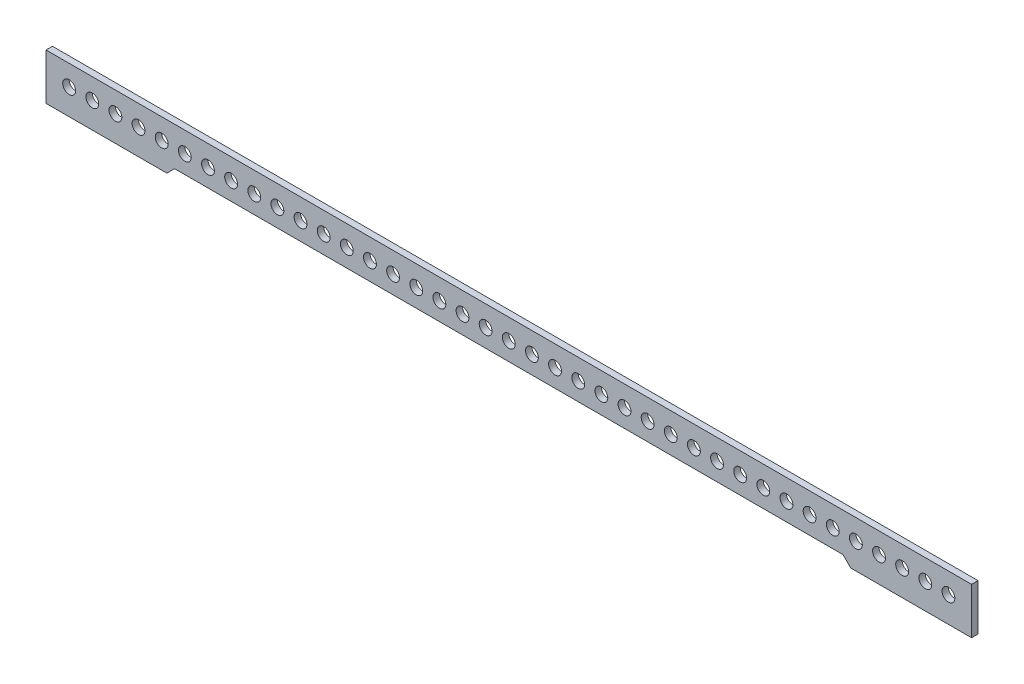
SolidWorks part; units mm, degrees
ref_plane "Front Plane" through (0, 0, 0) normal (0, 0, 1) x (1, 0, 0)
ref_plane "Top Plane" through (0, 0, 0) normal (0, 1, 0) x (1, 0, 0)
ref_plane "Right Plane" through (0, 0, 0) normal (1, 0, 0) x (0, 0, -1)
sketch "Sketch1" plane through (0, 0, 0) normal (0, 0, 1) x (1, 0, 0)
  line L0 (-228.6, 0) -> (228.6, 0)
  line L2 (228.6, -22.86) -> (168.91, -22.86)
  line L3 (168.91, -22.86) -> (165.1, -19.05)
  line L4 (165.1, -19.05) -> (-165.1, -19.05)
  line L5 (-165.1, -19.05) -> (-168.91, -22.86)
  line L6 (-168.91, -22.86) -> (-228.6, -22.86)
  line L8 (-228.6, -22.86) -> (-228.6, 0)
  line L9 (228.6, 0) -> (228.6, -22.86)
  point P0 (-165.1, -24.7914)
  dimension "D1" = 457.2
  dimension "D2" = 22.86
  dimension "D3" = 330.2
  dimension "D4" = 3.81
extrude "Boss-Extrude1" add sketch "Sketch1" along normal blind 3.175
sketch "Sketch3" plane through (0, 0, 3.175) normal (0, 0, 1) x (1, 0, 0)
  line L0 (228.6, 0) -> (-228.6, 0) construction
  line L1 (-217.17, -10.16) -> (-228.6, -10.16) construction
  line L2 (-217.17, -10.16) -> (-205.74, -10.16) construction
  line L3 (217.17, -10.16) -> (228.6, -10.16) construction
  line L4 (-228.6, 0) -> (-228.6, -22.86) construction
  line L5 (228.6, -22.86) -> (228.6, 0) construction
  circle A0 centre (-217.17, -10.16) radius 3.175
  circle A1 centre (-205.74, -10.16) radius 3.175
  circle A2 centre (-194.31, -10.16) radius 3.175
  circle A3 centre (-182.88, -10.16) radius 3.175
  circle A4 centre (-171.45, -10.16) radius 3.175
  circle A5 centre (-160.02, -10.16) radius 3.175
  circle A6 centre (-148.59, -10.16) radius 3.175
  circle A7 centre (-137.16, -10.16) radius 3.175
  circle A8 centre (-125.73, -10.16) radius 3.175
  circle A9 centre (-114.3, -10.16) radius 3.175
  circle A10 centre (-102.87, -10.16) radius 3.175
  circle A11 centre (-91.44, -10.16) radius 3.175
  circle A12 centre (-80.01, -10.16) radius 3.175
  circle A13 centre (-68.58, -10.16) radius 3.175
  circle A14 centre (-57.15, -10.16) radius 3.175
  circle A15 centre (-45.72, -10.16) radius 3.175
  circle A16 centre (-34.29, -10.16) radius 3.175
  circle A17 centre (-22.86, -10.16) radius 3.175
  circle A18 centre (-11.43, -10.16) radius 3.175
  circle A19 centre (0, -10.16) radius 3.175
  circle A20 centre (11.43, -10.16) radius 3.175
  circle A21 centre (22.86, -10.16) radius 3.175
  circle A22 centre (34.29, -10.16) radius 3.175
  circle A23 centre (45.72, -10.16) radius 3.175
  circle A24 centre (57.15, -10.16) radius 3.175
  circle A25 centre (68.58, -10.16) radius 3.175
  circle A26 centre (80.01, -10.16) radius 3.175
  circle A27 centre (91.44, -10.16) radius 3.175
  circle A28 centre (102.87, -10.16) radius 3.175
  circle A29 centre (114.3, -10.16) radius 3.175
  circle A30 centre (125.73, -10.16) radius 3.175
  circle A31 centre (137.16, -10.16) radius 3.175
  circle A32 centre (148.59, -10.16) radius 3.175
  circle A33 centre (160.02, -10.16) radius 3.175
  circle A34 centre (171.45, -10.16) radius 3.175
  circle A35 centre (182.88, -10.16) radius 3.175
  circle A36 centre (194.31, -10.16) radius 3.175
  circle A37 centre (205.74, -10.16) radius 3.175
  circle A38 centre (217.17, -10.16) radius 3.175
  dimension "D1" = 6.35
  dimension "D2" = 10.16
  dimension "D5" = 11.43
  dimension "D4" = 39
extrude "Cut-Extrude2" cut sketch "Sketch3" against normal through all
